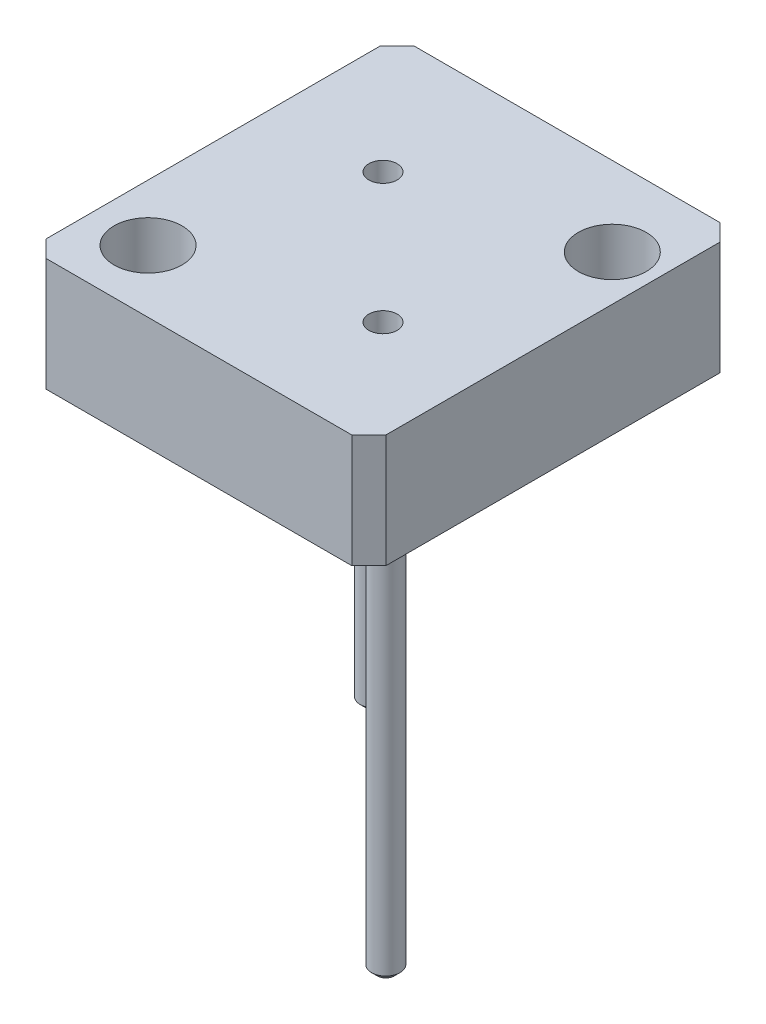
SolidWorks part; units mm, degrees
ref_plane "Front Plane" through (0, 0, 0) normal (0, 0, 1) x (1, 0, 0)
ref_plane "Top Plane" through (0, 0, 0) normal (0, 1, 0) x (1, 0, 0)
ref_plane "Right Plane" through (0, 0, 0) normal (1, 0, 0) x (0, 0, -1)
sketch "Sketch1" plane through (0, 0, 0) normal (0, 1, 0) x (1, 0, 0)
  line L1 (0, 0) -> (60, 0)
  line L2 (0, 0) -> (0, 65)
  line L3 (0, 65) -> (60, 65)
  line L4 (60, 0) -> (60, 65)
  dimension "D1" = 65
  dimension "D2" = 60
extrude "Boss-Extrude1" add sketch "Sketch1" along normal blind 20
sketch "Sketch2" plane through (0, 20, 0) normal (0, 1, 0) x (1, 0, 0)
  line L1 (19.5, 43) -> (42.5, 43)
  line L2 (19.5, 43) -> (19.5, 20)
  line L3 (19.5, 20) -> (42.5, 20)
  line L4 (42.5, 43) -> (42.5, 20)
  line L9 (0, 65) -> (0, 0) construction
  line L11 (60, 65) -> (0, 65) construction
  line L12 (0, 0) -> (60, 0) construction
  line L13 (60, 0) -> (60, 65) construction
  circle A0 centre (19.5, 43) radius 2.5
  circle A1 centre (42.5, 20) radius 2.5
  circle A2 centre (52, 11) radius 2.5
  circle A3 centre (10, 51) radius 2.5
  circle A4 centre (52, 51) radius 6
  circle A5 centre (10, 11) radius 6
  point P14 (0, 0)
  point P15 (0, 0)
  point P16 (0, 0)
  dimension "D3" = 5
  dimension "D4" = 5
  dimension "D5" = 5
  dimension "D6" = 12
  dimension "D1" = 23
  dimension "D2" = 23
  dimension "D7" = 22
  dimension "D8" = 40
  dimension "D9" = 58
  dimension "D10" = 58
  dimension "D11" = 42
  dimension "D12" = 19.5
extrude "Cut-Extrude1" cut sketch "Sketch2" against normal through all contours A4 | A5 region at (52, 20, -51) region at (10, 20, -11)
extrude "Cut-Extrude2" cut sketch "Sketch2<3>" against normal blind 5 contours A0 | A1
sketch "Sketch2<3>" plane through (0, 20, 0) normal (0, 1, 0) x (1, 0, 0) same geometry as "Sketch2"
extrude "Boss-Extrude2" add sketch "Sketch2<4>" against normal blind 90 contours A2 | A3 region at (52, 20, -11)
sketch "Sketch2<4>" plane through (0, 20, 0) normal (0, 1, 0) x (1, 0, 0) same geometry as "Sketch2"
chamfer "Chamfer1" distance 1 angle 45 2 edges at (52, -70, -8.5) (10, -70, -48.5)
chamfer "Chamfer2" distance 3 angle 45 4 edges at (60, 10, -65) (60, 10, 0) (0, 10, 0) (0, 10, -65)
